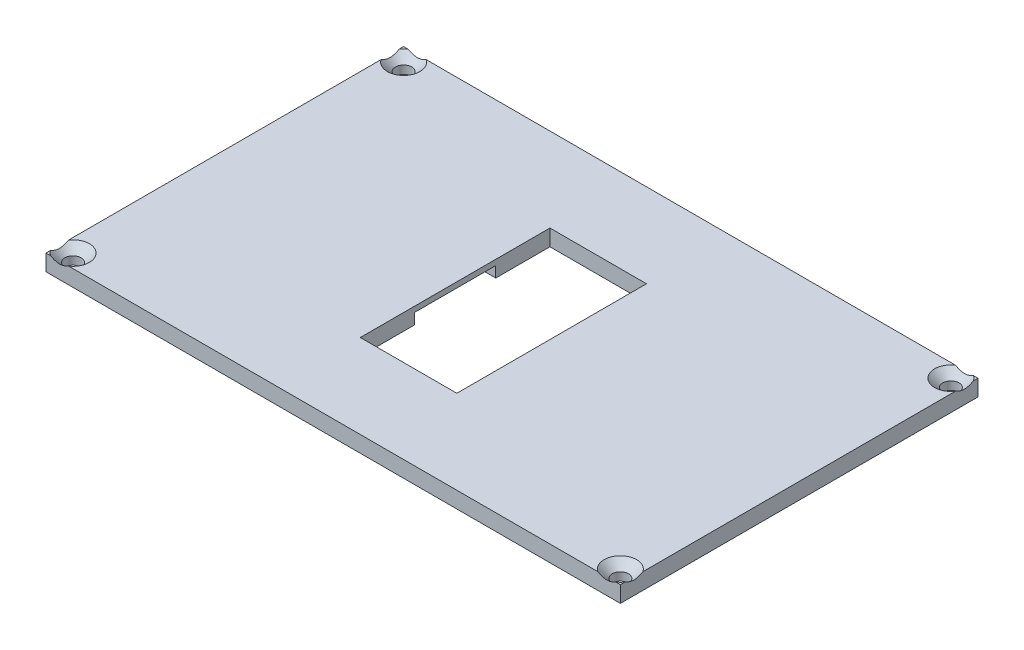
SolidWorks part; units mm, degrees
ref_plane "Alzado" through (0, 0, 0) normal (0, 0, 1) x (1, 0, 0)
ref_plane "Planta" through (0, 0, 0) normal (0, 1, 0) x (1, 0, 0)
ref_plane "Vista lateral" through (0, 0, 0) normal (1, 0, 0) x (0, 0, -1)
sketch "Croquis1" plane through (0, 0, 0) normal (0, 1, 0) x (1, 0, 0)
  line L1 (-42.3499, 29.4444) -> (63.6501, 29.4444)
  line L2 (-42.3499, 29.4444) -> (-42.3499, -36.5556)
  line L3 (-42.3499, -36.5556) -> (63.6501, -36.5556)
  line L4 (63.6501, 29.4444) -> (63.6501, -36.5556)
  dimension "D1" = 106
  dimension "D2" = 66
extrude "Saliente-Extruir1" add sketch "Croquis1" along normal blind 3
sketch "Croquis2" plane through (0, 3, 0) normal (0, 1, 0) x (1, 0, 0)
  line L0 (63.6501, 29.4444) -> (-42.3499, 29.4444) construction
  line L1 (0.1501, 13.9444) -> (17.9697, 13.9444)
  line L2 (0.1501, 13.9444) -> (0.1501, -21.0556)
  line L3 (0.1501, -21.0556) -> (17.9697, -21.0556)
  line L4 (17.9697, 13.9444) -> (17.9697, -21.0556)
  line L6 (-42.3499, 29.4444) -> (-42.3499, -36.5556) construction
  dimension "D1" = 35
  dimension "D2" = 17.8195
  dimension "D3" = 15.5
  dimension "D4" = 42.5
extrude "Cortar-Extruir1" cut sketch "Croquis2" against normal blind 3
sketch "Croquis3" plane through (0, 0, 0) normal (0, -1, 0) x (1, 0, 0)
  line L0 (17.9697, 21.0556) -> (17.9697, -13.9444) construction
  line L1 (17.9697, 9.0556) -> (23.9697, 9.0556)
  line L2 (17.9697, 9.0556) -> (17.9697, -1.9444)
  line L3 (17.9697, -1.9444) -> (23.9697, -1.9444)
  line L4 (23.9697, 9.0556) -> (23.9697, -1.9444)
  line L5 (17.9697, -13.9444) -> (0.1501, -13.9444) construction
  line L6 (0.1501, 21.0556) -> (17.9697, 21.0556) construction
  line L7 (0.1501, -13.9444) -> (0.1501, 21.0556) construction
  line L8 (0.1501, 11.0556) -> (-5.8499, 11.0556)
  line L9 (0.1501, 11.0556) -> (0.1501, -3.9444)
  line L10 (0.1501, -3.9444) -> (-5.8499, -3.9444)
  line L11 (-5.8499, 11.0556) -> (-5.8499, -3.9444)
  dimension "D1" = 12
  dimension "D2" = 12
  dimension "D3" = 6
  dimension "D4" = 10
  dimension "D5" = 10
  dimension "D6" = 6
extrude "Cortar-Extruir2" cut sketch "Croquis3" against normal blind 2
sketch "Croquis4" plane through (0, 3, 0) normal (0, 1, 0) x (1, 0, 0)
  line L0 (63.6501, 29.4444) -> (-42.3499, 29.4444) construction
  line L1 (-42.3499, 29.4444) -> (-42.3499, -36.5556) construction
  line L2 (63.6501, -36.5556) -> (63.6501, 29.4444) construction
  line L3 (-42.3499, -36.5556) -> (63.6501, -36.5556) construction
  circle A0 centre (-39.8499, 26.9444) radius 1.5
  circle A1 centre (61.1501, 26.9444) radius 1.5
  circle A2 centre (61.1501, -34.0556) radius 1.5
  circle A3 centre (-39.8499, -34.0556) radius 1.5
  dimension "D1" = 2.5
  dimension "D3" = 2.5
  dimension "D5" = 2.5
  dimension "D2" = 2.5
extrude "Cortar-Extruir3" cut sketch "Croquis4" against normal blind 4
chamfer "Chaflán1" distance 1.5 angle 45 4 edges at (61.1501, 3, 35.5556) (-39.8499, 3, 35.5556) (-39.8499, 3, -25.4444) (61.1501, 3, -25.4444)
